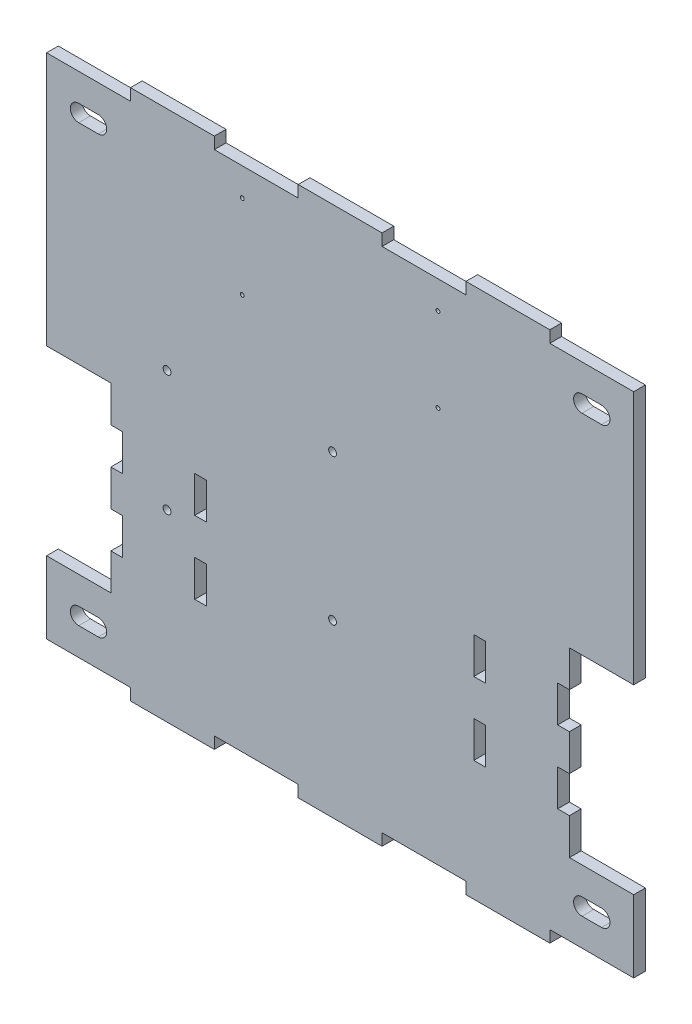
SolidWorks part; units mm, degrees
ref_plane "Front Plane" through (0, 0, 0) normal (0, 0, 1) x (1, 0, 0)
ref_plane "Top Plane" through (0, 0, 0) normal (0, 1, 0) x (1, 0, 0)
ref_plane "Right Plane" through (0, 0, 0) normal (1, 0, 0) x (0, 0, -1)
sketch "Sketch1" plane through (0, 0, 0) normal (0, 0, 1) x (1, 0, 0)
  line L1 (-133.35, 120.65) -> (133.35, 120.65)
  line L2 (-133.35, 120.65) -> (-133.35, -120.65)
  line L3 (-133.35, -120.65) -> (133.35, -120.65)
  line L4 (133.35, 120.65) -> (133.35, -120.65)
  line L5 (-133.35, 120.65) -> (133.35, -120.65) construction
  line L6 (-133.35, -120.65) -> (133.35, 120.65) construction
  point P0 (0, 0)
  dimension "D1" = 241.3
  dimension "D2" = 266.7
extrude "Boss-Extrude1" add sketch "Sketch1" along normal blind 5.334
sketch "Sketch2" plane through (0, 0, 0) normal (0, 0, -1) x (-1, 0, 0)
  line L0 (133.35, 120.65) -> (133.35, -120.65) construction
  line L1 (133.35, 0) -> (104.14, 0)
  line L2 (133.35, 0) -> (133.35, -82.55)
  line L3 (133.35, -82.55) -> (104.14, -82.55)
  line L4 (104.14, 0) -> (104.14, -82.55)
  line L5 (-133.35, -120.65) -> (-133.35, 120.65) construction
  line L6 (-133.35, 0) -> (-104.14, 0)
  line L7 (-133.35, 0) -> (-133.35, -82.55)
  line L8 (-133.35, -82.55) -> (-104.14, -82.55)
  line L9 (-104.14, 0) -> (-104.14, -82.55)
  line L10 (133.35, -120.65) -> (-133.35, -120.65) construction
  dimension "D1" = 82.55
  dimension "D2" = 82.55
  dimension "D3" = 38.1
  dimension "D4" = 38.1
  dimension "D5" = 29.21
  dimension "D6" = 29.21
extrude "Cut-Extrude1" cut sketch "Sketch2" against normal through all
sketch "Sketch9" plane through (0, 0, 5.334) normal (0, 0, 1) x (1, 0, 0)
  line L0 (-104.14, 0) -> (-104.14, -82.55) construction
  line L1 (-104.14, -16.51) -> (-98.806, -16.51)
  line L2 (-104.14, -16.51) -> (-104.14, -33.02)
  line L3 (-104.14, -33.02) -> (-98.806, -33.02)
  line L4 (-98.806, -16.51) -> (-98.806, -33.02)
  line L5 (-104.14, 0) -> (-98.806, 0) construction
  line L6 (-104.14, -49.53) -> (-98.806, -49.53)
  line L7 (-104.14, -49.53) -> (-104.14, -66.04)
  line L8 (-104.14, -66.04) -> (-98.806, -66.04)
  line L9 (-98.806, -49.53) -> (-98.806, -66.04)
  line L10 (-98.806, 0) -> (-98.806, -16.51) construction
  line L11 (-98.806, -33.02) -> (-98.806, -49.53) construction
  line L12 (-104.14, -82.55) -> (-98.806, -82.55) construction
  line L13 (-98.806, -82.55) -> (-98.806, -66.04) construction
  line L14 (0, -120.65) -> (0, 120.65) construction
  line L15 (-133.35, -120.65) -> (133.35, -120.65) construction
  line L16 (133.35, 120.65) -> (-133.35, 120.65) construction
  line L17 (98.806, -82.55) -> (98.806, -66.04) construction
  line L18 (104.14, -82.55) -> (98.806, -82.55) construction
  line L19 (98.806, -33.02) -> (98.806, -49.53) construction
  line L20 (98.806, 0) -> (98.806, -16.51) construction
  line L21 (104.14, 0) -> (98.806, 0) construction
  line L22 (98.806, -49.53) -> (98.806, -66.04)
  line L23 (104.14, -66.04) -> (98.806, -66.04)
  line L24 (104.14, -49.53) -> (104.14, -66.04)
  line L25 (104.14, -49.53) -> (98.806, -49.53)
  line L26 (98.806, -16.51) -> (98.806, -33.02)
  line L27 (104.14, -33.02) -> (98.806, -33.02)
  line L28 (104.14, -16.51) -> (104.14, -33.02)
  line L29 (104.14, -16.51) -> (98.806, -16.51)
  dimension "D1" = 5.334
extrude "Cut-Extrude2" cut sketch "Sketch9" against normal through all
sketch "Sketch23" plane through (0, 0, 5.334) normal (0, 0, 1) x (1, 0, 0)
  line L0 (-98.806, -24.765) -> (-61.976, -24.765) construction
  line L1 (-98.806, -33.02) -> (-98.806, -16.51) construction
  line L2 (-98.806, -16.51) -> (-60.706, -16.51) construction
  line L3 (-98.806, -33.02) -> (-60.706, -33.02) construction
  line L4 (-104.14, -41.275) -> (104.14, -41.275) construction
  line L5 (-104.14, -33.02) -> (-104.14, -49.53) construction
  line L6 (104.14, -49.53) -> (104.14, -33.02) construction
  line L7 (-98.806, -49.53) -> (-60.706, -49.53) construction
  line L8 (-98.806, -57.785) -> (-61.976, -57.785) construction
  line L9 (-98.806, -66.04) -> (-60.706, -66.04) construction
  line L10 (0, -120.65) -> (0, 120.65) construction
  line L11 (-133.35, -120.65) -> (133.35, -120.65) construction
  line L12 (133.35, 120.65) -> (-133.35, 120.65) construction
  line L13 (98.806, -66.04) -> (60.706, -66.04) construction
  line L14 (98.806, -49.53) -> (60.706, -49.53) construction
  line L15 (98.806, -33.02) -> (60.706, -33.02) construction
  line L16 (98.806, -16.51) -> (60.706, -16.51) construction
  line L17 (-60.706, -66.04) -> (-66.04, -66.04)
  line L18 (60.706, -16.51) -> (66.04, -16.51)
  line L19 (60.706, -16.51) -> (60.706, -33.02)
  line L20 (60.706, -33.02) -> (66.04, -33.02)
  line L21 (66.04, -16.51) -> (66.04, -33.02)
  line L22 (60.706, -49.53) -> (66.04, -49.53)
  line L23 (60.706, -49.53) -> (60.706, -66.04)
  line L24 (60.706, -66.04) -> (66.04, -66.04)
  line L25 (66.04, -49.53) -> (66.04, -66.04)
  line L26 (-66.04, -49.53) -> (-66.04, -66.04)
  line L27 (-60.706, -49.53) -> (-60.706, -66.04)
  line L28 (-60.706, -49.53) -> (-66.04, -49.53)
  line L29 (-60.706, -33.02) -> (-66.04, -33.02)
  line L30 (-66.04, -16.51) -> (-66.04, -33.02)
  line L31 (-60.706, -16.51) -> (-66.04, -16.51)
  line L32 (-60.706, -16.51) -> (-60.706, -33.02)
  line L33 (98.806, -16.51) -> (98.806, -33.02) construction
  dimension "D1" = 5.334
  dimension "D2" = 5.334
  dimension "D3" = 32.766
  dimension "D4" = 32.766
extrude "Cut-Extrude8" cut sketch "Sketch23" against normal through all
sketch "Sketch28" plane through (0, 0, 0) normal (0, 0, -1) x (-1, 0, 0)
  line L0 (133.35, -120.65) -> (-133.35, -120.65) construction
  line L1 (-133.35, -120.65) -> (-95.25, -120.65)
  line L2 (-133.35, -120.65) -> (-133.35, -115.316)
  line L3 (-133.35, -115.316) -> (-95.25, -115.316)
  line L4 (-95.25, -120.65) -> (-95.25, -115.316)
  line L5 (-57.15, -120.65) -> (-19.05, -120.65)
  line L6 (-57.15, -120.65) -> (-57.15, -115.316)
  line L7 (-57.15, -115.316) -> (-19.05, -115.316)
  line L8 (-19.05, -120.65) -> (-19.05, -115.316)
  line L9 (133.35, -82.55) -> (133.35, -120.65) construction
  line L10 (19.05, -120.65) -> (57.15, -120.65)
  line L11 (19.05, -120.65) -> (19.05, -115.316)
  line L12 (19.05, -115.316) -> (57.15, -115.316)
  line L13 (57.15, -120.65) -> (57.15, -115.316)
  line L14 (95.25, -120.65) -> (133.35, -120.65)
  line L16 (95.25, -115.316) -> (133.35, -115.316)
  line L17 (133.35, -120.65) -> (133.35, -115.316)
  line L18 (-95.25, -115.316) -> (-57.15, -115.316) construction
  line L19 (-19.05, -115.316) -> (19.05, -115.316) construction
  line L20 (95.25, -115.316) -> (57.15, -115.316) construction
  line L21 (133.35, 120.65) -> (133.35, -115.316) construction
  line L22 (133.35, -115.316) -> (133.5431, -115.1744) construction
  line L41 (95.25, -120.65) -> (95.25, -115.316)
  dimension "D1" = 5.334
extrude "Cut-Extrude13" cut sketch "Sketch28" against normal through all
sketch "Sketch29" plane through (0, 0, 0) normal (0, 0, -1) x (-1, 0, 0)
  line L0 (-133.35, 120.65) -> (133.35, 120.65) construction
  line L1 (-133.35, 120.65) -> (-95.25, 120.65)
  line L2 (-133.35, 120.65) -> (-133.35, 115.316)
  line L3 (-133.35, 115.316) -> (-95.25, 115.316)
  line L4 (-95.25, 120.65) -> (-95.25, 115.316)
  line L5 (-57.15, 120.65) -> (-19.05, 120.65)
  line L6 (-57.15, 120.65) -> (-57.15, 115.316)
  line L7 (-57.15, 115.316) -> (-19.05, 115.316)
  line L8 (-19.05, 120.65) -> (-19.05, 115.316)
  line L9 (133.35, 120.65) -> (133.35, 0) construction
  line L10 (19.05, 120.65) -> (57.15, 120.65)
  line L11 (19.05, 120.65) -> (19.05, 115.316)
  line L12 (19.05, 115.316) -> (57.15, 115.316)
  line L13 (57.15, 120.65) -> (57.15, 115.316)
  line L14 (95.25, 120.65) -> (133.35, 120.65)
  line L15 (95.25, 120.65) -> (95.25, 115.316)
  line L16 (95.25, 115.316) -> (133.35, 115.316)
  line L17 (133.35, 120.65) -> (133.35, 115.316)
  line L18 (-95.25, 115.316) -> (-57.15, 115.316) construction
  line L19 (19.05, 115.316) -> (-19.05, 115.316) construction
  line L20 (57.15, 115.316) -> (95.25, 115.316) construction
  dimension "D1" = 5.334
extrude "Cut-Extrude14" cut sketch "Sketch29" against normal through all
sketch "Sketch30" plane through (0, 0, 5.334) normal (0, 0, 1) x (1, 0, 0)
  circle A6 centre (-44.45, 102.616) radius 0.889
  circle A13 centre (44.45, 102.616) radius 0.889
  circle A60 centre (-44.45, 64.516) radius 0.889
  circle A67 centre (44.45, 64.516) radius 0.889
extrude "Cut-Extrude15" cut sketch "Sketch30" against normal through all
sketch "Sketch32" plane through (0, 0, 0) normal (0, 0, -1) x (-1, 0, 0)
  circle A0 centre (3.4305, -42.9775) radius 1.778 construction
  circle A1 centre (78.6145, -37.1355) radius 1.778 construction
  circle A2 centre (3.4305, 23.3165) radius 1.778 construction
  circle A3 centre (78.6145, 17.7285) radius 1.778 construction
  circle A4 centre (3.4305, -42.9775) radius 1.778
  circle A5 centre (78.6145, -37.1355) radius 1.778
  circle A6 centre (3.4305, 23.3165) radius 1.778
  circle A7 centre (78.6145, 17.7285) radius 1.778
extrude "Cut-Extrude16" cut sketch "Sketch32" against normal through all
sketch "Sketch35" plane through (0, 0, 5.334) normal (0, 0, 1) x (1, 0, 0)
  line L0 (0, 120.65) -> (0, -120.65) construction
  line L1 (19.05, 120.65) -> (-19.05, 120.65) construction
  line L2 (-19.05, -120.65) -> (19.05, -120.65) construction
  line L3 (-133.35, -98.933) -> (133.35, -98.933) construction
  line L4 (-133.35, -82.55) -> (-133.35, -115.316) construction
  line L5 (133.35, -115.316) -> (133.35, -82.55) construction
  line L6 (-118.745, -82.55) -> (-118.745, -115.316) construction
  line L7 (-104.14, -82.55) -> (-133.35, -82.55) construction
  line L8 (-133.35, -115.316) -> (-95.25, -115.316) construction
  line L9 (-114.3, -115.316) -> (-114.3, -82.55) construction
  line L10 (118.745, -82.55) -> (118.745, -115.316) construction
  line L11 (133.35, -82.55) -> (104.14, -82.55) construction
  line L12 (95.25, -115.316) -> (133.35, -115.316) construction
  line L13 (114.3, -115.316) -> (114.3, -82.55) construction
  line L14 (-109.855, -98.933) -> (-118.745, -98.933) construction
  line L15 (-109.855, -102.743) -> (-118.745, -102.743)
  line L16 (-109.855, -95.123) -> (-118.745, -95.123)
  line L17 (109.855, -98.933) -> (118.745, -98.933) construction
  line L18 (109.855, -95.123) -> (118.745, -95.123)
  line L19 (109.855, -102.743) -> (118.745, -102.743)
  line L20 (0, 0) -> (43.5068, 0) construction
  line L21 (109.855, 98.933) -> (118.745, 98.933) construction
  line L22 (109.855, 95.123) -> (118.745, 95.123)
  line L23 (109.855, 102.743) -> (118.745, 102.743)
  line L24 (-109.855, 98.933) -> (-118.745, 98.933) construction
  line L25 (-109.855, 102.743) -> (-118.745, 102.743)
  line L26 (-109.855, 95.123) -> (-118.745, 95.123)
  arc A0 (-109.855, -102.743) -> (-109.855, -95.123) centre (-109.855, -98.933) ccw
  arc A1 (-118.745, -95.123) -> (-118.745, -102.743) centre (-118.745, -98.933) ccw
  arc A2 (109.855, -95.123) -> (109.855, -102.743) centre (109.855, -98.933) ccw
  arc A3 (118.745, -102.743) -> (118.745, -95.123) centre (118.745, -98.933) ccw
  arc A4 (109.855, 95.123) -> (109.855, 102.743) centre (109.855, 98.933) cw
  arc A5 (118.745, 102.743) -> (118.745, 95.123) centre (118.745, 98.933) cw
  arc A6 (-109.855, 102.743) -> (-109.855, 95.123) centre (-109.855, 98.933) cw
  arc A7 (-118.745, 95.123) -> (-118.745, 102.743) centre (-118.745, 98.933) cw
  point P30 (-114.3, -98.933)
  point P36 (114.3, -98.933)
  point P47 (114.3, 98.933)
  point P54 (-114.3, 98.933)
extrude "Cut-Extrude19" cut sketch "Sketch35" against normal through all
equation "\"MDF\"= .21in"
equation "\"Foamcore\"= .13in"
equation "\"Gmaterial\"= \"MDF\""
equation "\"D1@Sketch9\"=\"MDF\""
equation "\"D1@Sketch23\"=\"MDF\""
equation "\"D2@Sketch23\"=\"D1@Sketch23\""
equation "\"D1@Boss-Extrude1\"=\"MDF\""
equation "\"D3@Sketch23\"=1.29"
equation "\"D1@Sketch28\"=\"MDF\""
equation "\"D1@Sketch29\"=\"MDF\""
